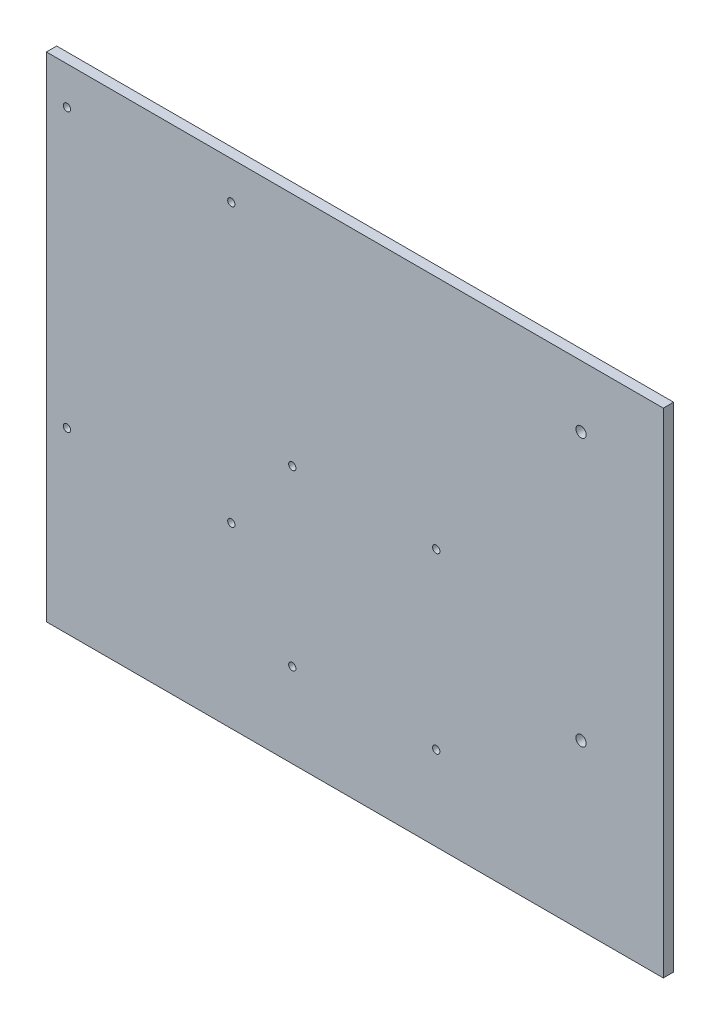
SolidWorks part; units mm, degrees
material "Acrylic (Medium-high impact)"
ref_plane "Front Plane" through (0, 0, 0) normal (0, 0, 1) x (1, 0, 0)
ref_plane "Top Plane" through (0, 0, 0) normal (0, 1, 0) x (1, 0, 0)
ref_plane "Right Plane" through (0, 0, 0) normal (1, 0, 0) x (0, 0, -1)
sketch "Sketch1" plane through (0, 0, 0) normal (0, 0, 1) x (1, 0, 0)
  line L1 (0, 0) -> (381, 0)
  line L2 (0, 0) -> (0, 304.8)
  line L3 (0, 304.8) -> (381, 304.8)
  line L4 (381, 0) -> (381, 304.8)
  dimension "D1" = 381
  dimension "D2" = 304.8
extrude "Boss-Extrude1" add sketch "Sketch1" along normal blind 6.35
hole_wizard "M4 Clearance Hole1" positions "Sketch4" profile "Sketch5" hole size "M4" standard "ANSI Metric" end condition through all
sketch "Sketch4" plane through (0, 0, 6.35) normal (0, 0, 1) x (1, 0, 0)
  line L6 (0, 304.8) -> (0, 0) construction
  line L7 (0, 0) -> (381, 0) construction
  point P0 (12.7, 110)
  point P2 (114.2, 110)
  point P15 (12.7, 281.5)
  point P17 (114.2, 281.5)
  dimension "D1" = 101.5
  dimension "D2" = 110
  dimension "D3" = 12.7
  dimension "D4" = 171.5
sketch "Sketch5" plane through (12.7, 110, 6.35) normal (1, 0, 0) x (0, -1, 0)
  line L0 (0, 0) -> (0, 6.35)
  line L1 (0, 6.35) -> (2.25, 6.35)
  line L2 (2.25, 6.35) -> (2.25, 0)
  line L5 (2.25, 0) -> (0, 0)
  line L11 (0, -6.35) -> (0, 107.95) construction
  dimension "Thru Hole Dia." = 4.5
  dimension "Thru Hole Depth" = 6.35
sketch "Sketch3" plane through (0, 0, 6.35) normal (0, 0, 1) x (1, 0, 0)
  line L0 (0, 0) -> (381, 0) construction
  line L3 (381, 0) -> (381, 304.8) construction
  line L4 (285.75, 293.3324) -> (374.65, 293.3324) construction
  line L5 (285.75, 293.3324) -> (285.75, 20.2824) construction
  line L6 (285.75, 20.2824) -> (374.65, 20.2824) construction
  line L7 (374.65, 293.3324) -> (374.65, 20.2824) construction
  line L8 (285.75, 293.3324) -> (374.65, 20.2824) construction
  line L9 (285.75, 20.2824) -> (374.65, 293.3324) construction
  circle A0 centre (330.2, 101.6) radius 3.175
  circle A1 centre (330.2, 266.7) radius 3.175
  point P4 (0, 0)
  point P5 (326.2818, 156.8074)
  point P12 (330.2, 156.8074)
  dimension "D2" = 6.35
  dimension "D3" = 6.35
  dimension "D1" = 165.1
  dimension "D4" = 101.6
  dimension "D5" = 88.9
  dimension "D6" = 273.05
extrude "Cut-Extrude2" cut sketch "Sketch3" against normal through all
extrude "Cut-Extrude5" cut sketch "Sketch8" against normal blind 6.35
sketch "Sketch8" plane through (190.518, -5.8963, 6.35) normal (0, 0, 1) x (1, 0, 0)
  circle A0 centre (-38.6719, 165.0958) radius 2.2542
  circle A1 centre (50.2281, 165.0958) radius 2.2542
  circle A2 centre (-38.6719, 57.9129) radius 2.2542
  circle A3 centre (50.2281, 57.9129) radius 2.2542
